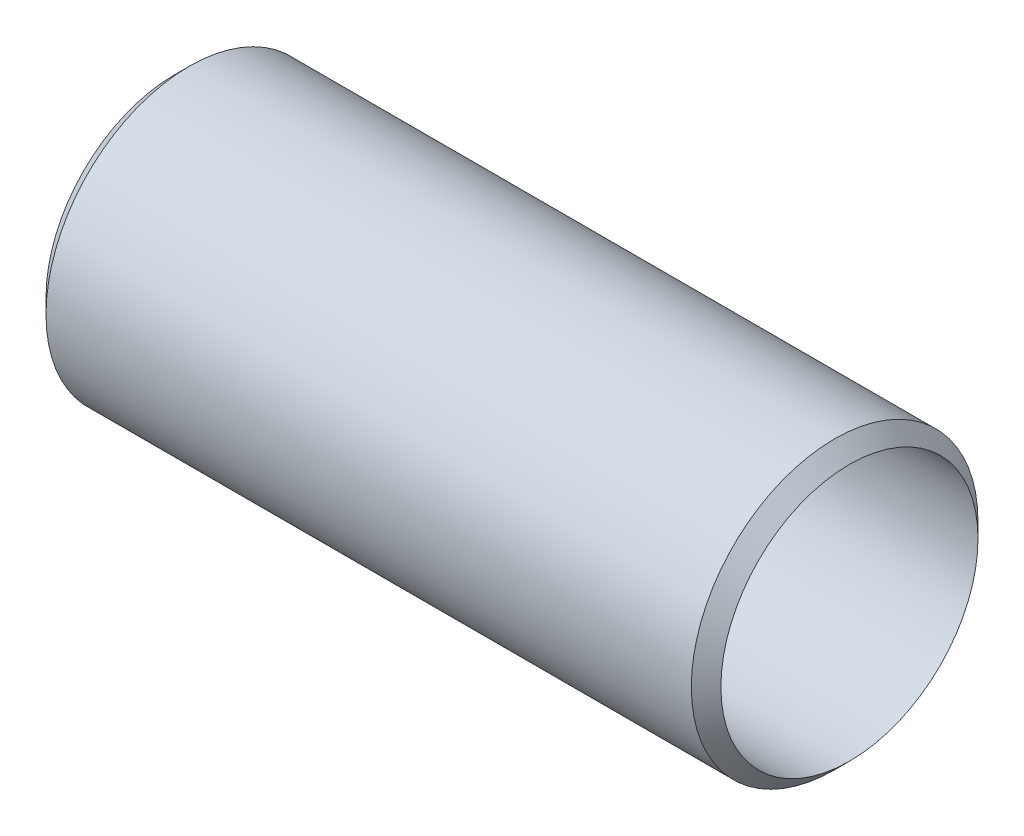
SolidWorks part; units mm, degrees
material "AISI 1035 Steel (SS)"
ref_plane "Front Plane" through (0, 0, 0) normal (0, 0, 1) x (1, 0, 0)
ref_plane "Top Plane" through (0, 0, 0) normal (0, 1, 0) x (1, 0, 0)
ref_plane "Right Plane" through (0, 0, 0) normal (1, 0, 0) x (0, 0, -1)
sketch "Sketch1" plane through (0, 0, 0) normal (1, 0, 0) x (0, 0, -1)
  circle A0 centre (0, 0) radius 28.321
  dimension "D1" = 56.642
extrude "Boss-Extrude1" add sketch "Sketch1" along normal blind 66.675 and the other way blind 66.675
sketch "Sketch2" plane through (66.675, 0, 0) normal (1, 0, 0) x (0, 0, -1)
  point P0 (0, 0)
hole_wizard "#97 (2) Diameter Hole1" positions "Sketch2" profile "Sketch3" hole size "#97" standard "ANSI Inch" end condition through all
sketch "Sketch3" plane through (66.675, 0, 0) normal (0, 1, 0) x (0, 0, -1)
  line L0 (0, 0) -> (0, 133.35)
  line L1 (0, 133.35) -> (25.4, 133.35)
  line L2 (25.4, 133.35) -> (25.4, 0)
  line L5 (25.4, 0) -> (0, 0)
  line L11 (0, -6.35) -> (0, 107.95) construction
  dimension "Thru Hole Dia." = 50.8
  dimension "Thru Hole Depth" = 133.35
chamfer "Chamfer1" distance 2.921 angle 45 2 edges at (-66.675, 0, -28.321) (66.675, 0, -28.321)
